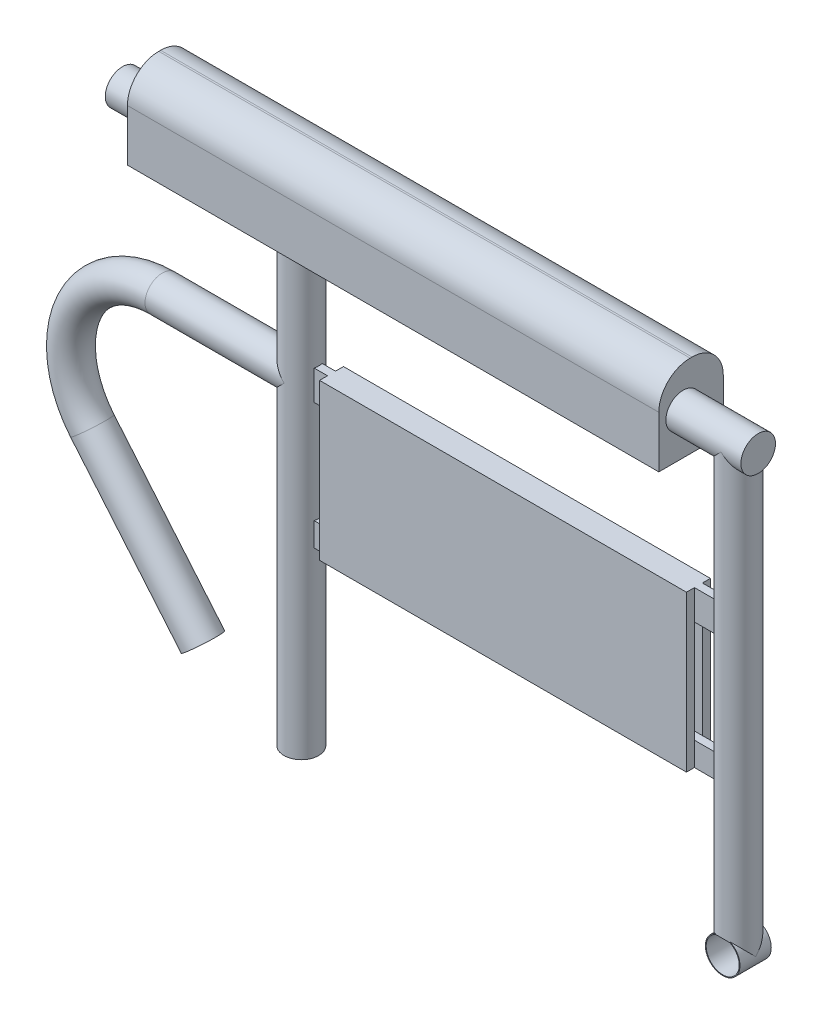
SolidWorks part; units mm, degrees
ref_plane "Front Plane" through (0, 0, 0) normal (0, 0, 1) x (1, 0, 0)
ref_plane "Top Plane" through (0, 0, 0) normal (0, 1, 0) x (1, 0, 0)
ref_plane "Right Plane" through (0, 0, 0) normal (1, 0, 0) x (0, 0, -1)
sketch "Sketch1" plane through (0, 0, 0) normal (0, 1, 0) x (1, 0, 0)
  circle A0 centre (0, 0) radius 11.065
  circle A1 centre (279.4, 0) radius 11.065
  dimension "D1" = 22.13
  dimension "D2" = 22.13
  dimension "D3" = 279.4
extrude "Extrude1" add sketch "Sketch1" along normal blind 279.4
sketch "Sketch2" plane through (0, 0, 0) normal (1, 0, 0) x (0, 0, -1)
  line L0 (11.065, 279.4) -> (-11.065, 279.4) construction
  circle A0 centre (0, 279.4) radius 11.065
extrude "Extrude2" add sketch "Sketch2" along normal blind 292.1 and the other way blind 114.3
sketch "Sketch3" plane through (-114.3, 0, 0) normal (-1, 0, 0) x (0, 0, 1)
  circle A0 centre (0, 177.8) radius 11.065
  circle A1 centre (0, 279.4) radius 11.065 construction
  dimension "D1" = 101.6
extrude "Extrude3" add sketch "Sketch3" against normal blind 114.3
sketch "Sketch5" plane through (0, 0, 0) normal (0, 0, 1) x (1, 0, 0)
  line L0 (-114.3, 188.865) -> (-114.3, 166.735) construction
  line L1 (-139.7, 188.865) -> (-88.9, 188.865)
  line L2 (-139.7, 188.865) -> (-139.7, 166.735)
  line L3 (-139.7, 166.735) -> (-88.9, 166.735)
  line L4 (-88.9, 188.865) -> (-88.9, 166.735)
  line L5 (-139.7, 188.865) -> (-88.9, 166.735) construction
  line L6 (-139.7, 166.735) -> (-88.9, 188.865) construction
  line L7 (-114.3, 166.735) -> (-11.065, 166.735) construction
  point P0 (-114.3, 177.8)
  dimension "D1" = 25.4
extrude "Extrude5" cut sketch "Sketch5" against normal through all and the other way through all
sketch "Sketch7" plane through (-88.9, 0, 0) normal (-1, 0, 0) x (0, 0, 1)
  line L0 (0, 119.38) -> (28.8371, 119.38)
  circle A0 centre (0, 177.8) radius 11.065
  dimension "D1" = 58.42
revolve "Revolve-Thin3" add sketch "Sketch7" angle 130 about L0 body kept at (11.065, 0, 0) wall 10
sketch "Sketch10" plane through (-95.5145, 113.8298, 0) normal (0.6428, -0.766, 0) x (0.766, 0.6428, 0)
  circle A0 centre (-49.7854, 0) radius 11.065
extrude "Extrude6" add sketch "Sketch10" along normal blind 110.1
sketch "Sketch11" plane through (0, 0, 0) normal (1, 0, 0) x (0, 0, -1)
  line L1 (2.55, 168.275) -> (-2.55, 168.275)
  line L2 (2.55, 168.275) -> (2.55, 187.325)
  line L3 (2.55, 187.325) -> (-2.55, 187.325)
  line L4 (-2.55, 168.275) -> (-2.55, 187.325)
  line L5 (2.55, 168.275) -> (-2.55, 187.325) construction
  line L6 (2.55, 187.325) -> (-2.55, 168.275) construction
  line L7 (2.55, 87.6717) -> (-2.55, 87.6717)
  line L8 (2.55, 87.6717) -> (2.55, 102.8283)
  line L9 (2.55, 102.8283) -> (-2.55, 102.8283)
  line L10 (-2.55, 87.6717) -> (-2.55, 102.8283)
  line L11 (2.55, 87.6717) -> (-2.55, 102.8283) construction
  line L12 (2.55, 102.8283) -> (-2.55, 87.6717) construction
  point P0 (0, 177.8)
  point P6 (0, 95.25)
  dimension "D1" = 19.05
  dimension "D2" = 5.1
  dimension "D3" = 82.55
extrude "Extrude7" add sketch "Sketch11" along normal blind 279.4
sketch "Sketch12" plane through (0, 0, 2.55) normal (0, 0, 1) x (1, 0, 0)
  line L0 (268.6328, 187.325) -> (10.7672, 187.325) construction
  line L1 (19.2926, 187.325) -> (253.8741, 187.325)
  line L2 (19.2926, 187.325) -> (19.2926, 87.6717)
  line L3 (19.2926, 87.6717) -> (253.8741, 87.6717)
  line L4 (253.8741, 187.325) -> (253.8741, 87.6717)
  line L5 (268.6328, 87.6717) -> (10.7672, 87.6717) construction
extrude "Extrude8" add sketch "Sketch12" along normal blind 5.1
sketch "Sketch13" plane through (0, 0, 0) normal (0, 0, 1) x (1, 0, 0)
  line L0 (268.335, 0) -> (290.465, 0) construction
  circle A0 centre (279.4, 0) radius 11.065
  circle A1 centre (279.4, 0) radius 10.565
  dimension "D1" = 0.5
extrude "Extrude9" add sketch "Sketch13" along normal blind 10 and the other way blind 10
sketch "Sketch14" plane through (0, 0, -10) normal (0, 0, -1) x (-1, 0, 0)
  line L0 (-289.965, 0) -> (-268.835, 0) construction
  circle A0 centre (-279.4, 0) radius 10.565
extrude "Extrude10" cut sketch "Sketch14" against normal through all and the other way through all
sketch "Sketch15" plane through (0, 0, 0) normal (0, -1, 0) x (1, 0, 0)
  circle A0 centre (0, 0) radius 11.065
extrude "Extrude11" add sketch "Sketch15" along normal blind 28.4
mirror "Mirror1" about plane through (0, 0, 0) normal (0, 0, 1) of "Extrude8"
ref_plane "Plane1" through (0, 270, 0) normal (0, 1, 0) x (-1, 0, 0)
sketch "Sketch16" plane through (0, 270, 0) normal (0, 1, 0) x (-1, 0, 0)
  line L1 (-244.1187, 15.5492) -> (95.6319, 15.5492)
  line L2 (-244.1187, 15.5492) -> (-244.1187, -25.6562)
  line L3 (-244.1187, -25.6562) -> (95.6319, -25.6562)
  line L4 (95.6319, 15.5492) -> (95.6319, -25.6562)
extrude "Extrude12" add sketch "Sketch16" along normal blind 36 and the other way blind 17
fillet "Fillet1" radius 20 1 edges at (74.2434, 306, 15.5492)
fillet "Fillet2" radius 20 1 edges at (74.2434, 306, -25.6562)
fillet "Fillet3" radius 5 1 edges at (74.2434, 253, -25.6562)
